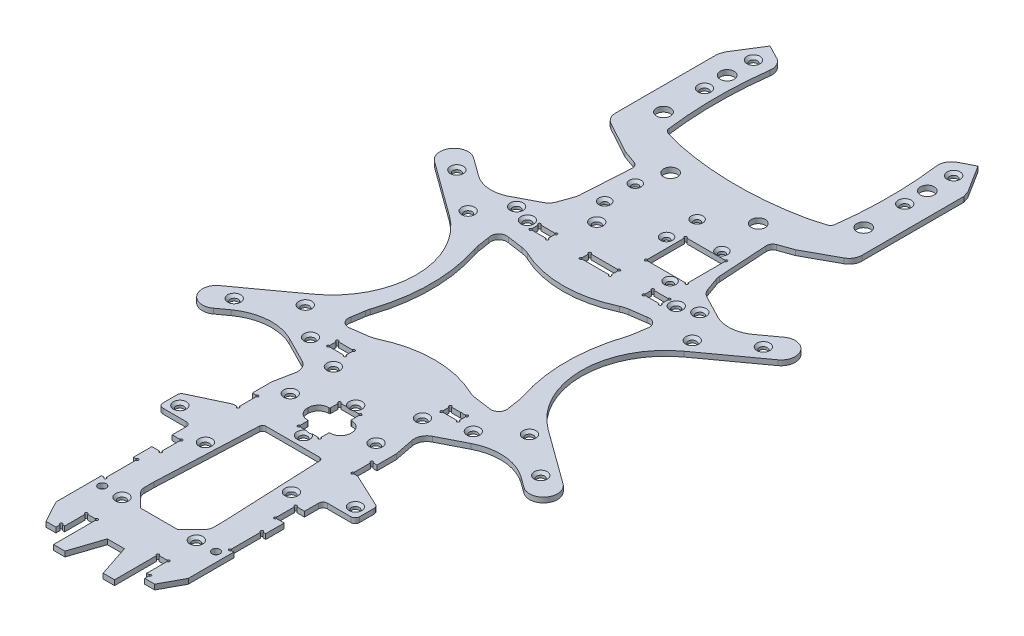
SolidWorks part; units mm, degrees
other "细节项目1"
other "细节项目5"
material "Thornel VCB-20 碳布"
ref_plane "前视基准面" through (0, 0, 0) normal (0, 0, 1) x (1, 0, 0)
ref_plane "上视基准面" through (0, 0, 0) normal (0, 1, 0) x (1, 0, 0)
ref_plane "右视基准面" through (0, 0, 0) normal (1, 0, 0) x (0, 0, -1)
sketch "草图1" plane through (0, 0, 0) normal (0, 1, 0) x (1, 0, 0)
  line L0 (-126.4995, 0) -> (116.8967, 0) construction
  line L1 (121.619, 121.619) -> (-121.619, -121.619) construction
  line L2 (0, 104.5414) -> (0, -99.6328) construction
  line L3 (-108.3893, 108.3893) -> (124.9236, -124.9236) construction
  line L4 (0, 0) -> (86.3378, -62.728) construction
  line L5 (15.4, 65.75) -> (23.6, 65.75)
  line L6 (15.4, 50.25) -> (15.4, 65.75)
  line L19 (15.4, 50.25) -> (23.6, 50.25)
  line L20 (30.4719, 81.4909) -> (48.4165, 91.3178)
  line L21 (0, 82.79) -> (0, 88.225) construction
  line L23 (-25.278, 96.1016) -> (-31.2014, 97.7723)
  line L25 (24.5, -95.1) -> (26.0011, -95.1) construction
  line L35 (67.5025, -42.245) -> (46.103, -26.6974)
  line L38 (-16.7464, -105.1066) -> (-17.9066, -103.9464) construction
  line L39 (-48.4165, 91.3178) -> (-48.4165, 134.3222)
  line L40 (-30.4719, 81.4909) -> (-48.4165, 91.3178)
  line L42 (26.0011, -95.1) -> (26.0011, -102.35)
  line L59 (-47.6512, 136.6895) -> (-40.8695, 147.4648)
  line L64 (15.4, 58) -> (27.0301, 58) construction
  line L65 (19.5, 65.75) -> (19.5, 50.25) construction
  line L66 (23.6, 65.75) -> (23.6, 50.25)
  line L69 (-39.335, 68.135) -> (3.7462, 68.135) construction
  line L72 (26.0011, -102.35) -> (22.5, -102.35)
  line L80 (-18.6137, -103.9464) -> (-19.7036, -105.0363) construction
  line L82 (4.1009, -74) -> (4.1009, -71.0475)
  line L83 (-3.6009, -74.5) -> (3.6009, -74.5)
  line L84 (3.6009, -58.5) -> (-3.5991, -58.5)
  line L85 (4.1009, -59) -> (4.1009, -61.9525)
  line L86 (-4.1009, -74) -> (-4.1009, -71.0461)
  line L87 (-4.1009, -61.9511) -> (-4.1009, -58.9981)
  line L88 (-4.5484, -70.6961) -> (-4.4509, -70.6961)
  line L89 (-8.5484, -66.6961) -> (-8.5484, -66.3011)
  line L90 (8.5484, -66.6975) -> (8.5484, -66.3025)
  line L91 (4.4509, -70.6975) -> (4.5484, -70.6975)
  line L92 (4.5484, -62.3025) -> (4.4509, -62.3025)
  line L93 (-4.5484, -62.3011) -> (-4.4509, -62.3011)
  line L97 (19, -62.5) -> (19, -100.5) construction
  line L98 (19, -100.5) -> (-19, -100.5) construction
  line L99 (-19, -62.5) -> (-19, -100.5) construction
  line L100 (22.5, -102.35) -> (22.5, -110.35)
  line L101 (16.1, -146) -> (16.1, -154.5)
  line L102 (16.1, -146) -> (12, -146)
  line L103 (12, -146) -> (12, -163)
  line L104 (17.45, -154.5) -> (16.1, -154.5)
  line L105 (17.45, -156.6) -> (17.45, -154.5)
  line L106 (-3.3584, -150.5) -> (-7.5, -163)
  line L107 (-7.5, -163) -> (-12, -163)
  line L108 (21.3534, -156.6) -> (17.45, -156.6)
  line L109 (-17.45, -156.6) -> (-17.45, -154.5)
  line L110 (-17.45, -154.5) -> (-16.1, -154.5)
  line L111 (-12, -146) -> (-12, -163)
  line L112 (-16.1, -146) -> (-12, -146)
  line L113 (-16.1, -146) -> (-16.1, -154.5)
  line L114 (7.5, -163) -> (12, -163)
  line L115 (-3.3584, -150.5) -> (3.3584, -150.5)
  line L116 (3.3584, -150.5) -> (7.5, -163)
  line L117 (-21.3534, -156.6) -> (-17.45, -156.6)
  line L118 (-13.5761, -121.8546) -> (-11.8487, -82.2911)
  line L119 (-12.5918, -128.1539) -> (-7.25, -133.5)
  line L120 (-7.25, -133.5) -> (7.25, -133.5)
  line L121 (-13.5793, -125.7684) -> (-13.5793, -122.0018)
  line L122 (22.5, -110.35) -> (26.0011, -110.35)
  line L123 (26.0011, -130.1) -> (26.0011, -148.0463)
  line L124 (26.0011, -148.0463) -> (21.3534, -156.6)
  line L125 (-26.0011, -148.0463) -> (-21.3534, -156.6)
  line L126 (-26.0011, -130.1) -> (-26.0011, -148.0463)
  line L127 (26.0011, -110.35) -> (26.0011, -117.6)
  line L128 (26.0011, -117.6) -> (24.5011, -117.6)
  line L129 (24.5011, -117.6) -> (24.5011, -130.1)
  line L130 (24.5011, -130.1) -> (26.0011, -130.1)
  line L132 (-24.5011, -130.1) -> (-26.0011, -130.1)
  line L133 (-24.5011, -117.6) -> (-24.5011, -130.1)
  line L134 (-26.0011, -117.6) -> (-24.5011, -117.6)
  line L135 (-26.0011, -110.35) -> (-26.0011, -117.6)
  line L136 (-22.5, -110.35) -> (-26.0011, -110.35)
  line L137 (-22.5, -102.35) -> (-22.5, -110.35)
  line L138 (-26.0011, -102.35) -> (-22.5, -102.35)
  line L139 (-26.0011, -95.1) -> (-26.0011, -102.35)
  line L140 (-24.5, -95.1) -> (-26.0011, -95.1) construction
  line L142 (-67.5025, 42.245) -> (-46.103, 26.6974)
  line L143 (-67.5025, -42.245) -> (-46.103, -26.6974)
  line L149 (48.4165, 91.3178) -> (48.4165, 134.3222)
  line L150 (0, -114.8485) -> (0, -146.3095) construction
  line L151 (-10.5, -81) -> (10.5, -81)
  line L152 (12.5918, -128.1539) -> (7.25, -133.5)
  line L153 (13.5793, -125.7684) -> (13.5793, -122.0018)
  line L154 (13.5761, -121.8546) -> (11.8487, -82.2911)
  line L155 (-19, -62.5) -> (19, -62.5) construction
  line L180 (67.5025, 42.245) -> (46.103, 26.6974)
  line L181 (44.0442, 32) -> (60.2246, 43.7557) construction
  line L183 (25.278, 96.1016) -> (31.2014, 97.7723)
  line L195 (61.0368, 51.1442) -> (53.9618, 46.0039)
  line L196 (30.4719, 81.4909) -> (34.3794, 54.2815)
  line L197 (-30.4719, 81.4909) -> (-34.3794, 54.2815)
  line L198 (-61.0368, 51.1442) -> (-53.9618, 46.0039)
  line L199 (57.02, -48.2258) -> (61.0368, -51.1442)
  line L200 (24.5, -64.7956) -> (24.5, -95.1) construction
  line L201 (-24.5, -64.7956) -> (-24.5, -95.1) construction
  line L202 (-57.02, -48.2258) -> (-61.0368, -51.1442)
  line L203 (26.0011, -95.1) -> (38.6804, -95.1)
  line L204 (38.6804, -95.1) -> (38.6804, -86.6)
  line L205 (38.6804, -86.6) -> (24.5, -79.9478)
  line L207 (-38.6804, -86.6) -> (-24.5, -79.9478)
  line L208 (-38.6804, -95.1) -> (-38.6804, -86.6)
  line L209 (-26.0011, -95.1) -> (-38.6804, -95.1)
  line L210 (-24.5, -64.7956) -> (-24.5, -79.9478) construction
  line L211 (-19.7036, -114.2434) -> (-18.5434, -115.4036) construction
  line L212 (-17.8363, -115.4036) -> (-16.7464, -114.3137) construction
  line L213 (-19.85, -105.3898) -> (-19.85, -113.8898) construction
  line L214 (-16.6, -105.4602) -> (-16.6, -113.9602) construction
  line L221 (-16.6, -105.4602) -> (-16.6, -108.5148) construction
  line L222 (-16.6, -108.5148) -> (-17.1, -109.0148) construction
  line L223 (-17.1, -109.0148) -> (-17.1, -110.2648) construction
  line L224 (-17.1, -110.2648) -> (-16.6, -110.7648) construction
  line L225 (-16.6, -110.7648) -> (-16.6, -113.9602) construction
  line L226 (-19.85, -109.6398) -> (-13.2317, -109.6398) construction
  line L227 (17.1, -110.2648) -> (16.6, -110.7648) construction
  line L228 (17.1, -109.0148) -> (17.1, -110.2648) construction
  line L229 (16.6, -108.5148) -> (17.1, -109.0148) construction
  line L230 (16.6, -105.4602) -> (16.6, -108.5148) construction
  line L231 (16.7464, -105.1066) -> (17.9066, -103.9464) construction
  line L232 (18.6137, -103.9464) -> (19.7036, -105.0363) construction
  line L233 (19.85, -105.3898) -> (19.85, -113.8898) construction
  line L234 (19.7036, -114.2434) -> (18.5434, -115.4036) construction
  line L235 (17.8363, -115.4036) -> (16.7464, -114.3137) construction
  line L236 (16.6, -110.7648) -> (16.6, -113.9602) construction
  line L237 (-24.5, -72.3717) -> (-22.5, -72.3717)
  line L238 (-22.5, -72.3717) -> (-22.5, -79.9478)
  line L239 (-22.5, -79.9478) -> (-24.5, -79.9478)
  line L240 (-24.5, -64.7956) -> (-24.5, -72.3717)
  line L241 (22.5, -79.9478) -> (24.5, -79.9478)
  line L242 (24.5, -64.7956) -> (24.5, -72.3717)
  line L243 (24.5, -72.3717) -> (22.5, -72.3717)
  line L244 (22.5, -72.3717) -> (22.5, -79.9478)
  line L245 (-40.8695, 147.4648) -> (-35.5107, 144.7028)
  line L246 (-47.6512, 136.6895) -> (-48.4165, 134.3222)
  line L247 (40.8695, 147.4648) -> (35.5107, 144.7028)
  line L248 (47.6512, 136.6895) -> (40.8695, 147.4648)
  line L249 (47.6512, 136.6895) -> (48.4165, 134.3222)
  circle A0 centre (10, 10) radius 1.075
  circle A1 centre (12.75, 12.75) radius 1.075
  circle A2 centre (15.25, 15.25) radius 1.55
  circle A3 centre (-15.25, 15.25) radius 1.55
  circle A4 centre (-12.75, 12.75) radius 1.075
  circle A5 centre (-10, 10) radius 1.075
  circle A6 centre (-10, -10) radius 1.075
  circle A7 centre (-12.75, -12.75) radius 1.075
  circle A8 centre (-15.25, -15.25) radius 1.55
  circle A9 centre (15.25, -15.25) radius 1.55
  circle A10 centre (12.75, -12.75) radius 1.075
  circle A11 centre (10, -10) radius 1.075
  circle A14 centre (28, -28) radius 3.15
  circle A15 centre (-28, -28) radius 3.15
  circle A16 centre (19.5, 68.2) radius 1.3
  circle A31 centre (19.5, 47.8) radius 1.3
  circle A34 centre (17.238, 84.7633) radius 2.75
  circle A35 centre (-17.238, 84.7633) radius 2.75
  circle A36 centre (-39.335, 104.0823) radius 2.75
  circle A37 centre (-39.335, 129.0823) radius 2.75
  circle A38 centre (-28, 28) radius 3.15
  circle A39 centre (28, 28) radius 3.15
  circle A43 centre (44.0442, -32) radius 1.55
  circle A44 centre (60.2246, -43.7557) radius 1.55
  circle A47 centre (-60.2246, -43.7557) radius 1.55
  circle A65 centre (-20.5, 74.15) radius 1.3
  circle A68 centre (-20.5, 62.12) radius 1.3
  circle A71 centre (-44.0442, -32) radius 1.55
  circle A72 centre (60.2246, 43.7557) radius 1.55
  circle A73 centre (44.0442, 32) radius 1.55
  circle A74 centre (-44.0442, 32) radius 1.55
  circle A75 centre (-60.2246, 43.7557) radius 1.55
  arc A77 (61.0368, -51.1442) -> (67.5025, -42.245) centre (64.2696, -46.6946) ccw
  arc A82 (-16.6, -105.4602) -> (-16.7464, -105.1066) centre (-17.1, -105.4602) ccw construction
  arc A83 (-17.9066, -103.9464) -> (-18.6137, -103.9464) centre (-18.2602, -104.3) ccw construction
  arc A84 (-19.85, -105.3898) -> (-19.7036, -105.0363) centre (-19.35, -105.3898) cw construction
  arc A85 (-4.1009, -74) -> (-3.6009, -74.5) centre (-4.1009, -74.5) ccw
  arc A86 (4.1009, -74) -> (3.6009, -74.5) centre (4.1009, -74.5) cw
  arc A87 (4.1009, -59) -> (3.6009, -58.5) centre (4.1009, -58.5) ccw
  arc A88 (-4.1009, -58.9981) -> (-3.5991, -58.5) centre (-4.0991, -58.4981) cw
  arc A89 (8.5484, -66.3025) -> (4.5484, -62.3025) centre (4.5484, -66.3025) ccw
  arc A90 (-4.5484, -62.3011) -> (-8.5484, -66.3011) centre (-4.5484, -66.3011) ccw
  arc A91 (-4.5484, -70.6961) -> (-8.5484, -66.6961) centre (-4.5484, -66.6961) cw
  arc A92 (8.5484, -66.6975) -> (4.5484, -70.6975) centre (4.5484, -66.6975) cw
  arc A93 (4.1009, -61.9525) -> (4.4509, -62.3025) centre (4.4509, -61.9525) ccw
  arc A94 (4.1009, -71.0475) -> (4.4509, -70.6975) centre (4.4509, -71.0475) cw
  arc A95 (-4.1009, -61.9511) -> (-4.4509, -62.3011) centre (-4.4509, -61.9511) cw
  arc A96 (-4.1009, -71.0461) -> (-4.4509, -70.6961) centre (-4.4509, -71.0461) ccw
  circle A103 centre (-22.35, -133.5) radius 1.55
  circle A104 centre (22.35, -133.5) radius 1.55
  circle A105 centre (-16.9, -98.4) radius 1.55
  circle A106 centre (16.9, -98.4) radius 1.55
  arc A107 (-10.5, -81) -> (-11.8487, -82.2911) centre (-10.5, -82.35) ccw
  arc A108 (-13.5793, -122.0018) -> (-13.5761, -121.8546) centre (-10.2043, -122.0018) cw
  arc A109 (-12.5918, -128.1539) -> (-13.5793, -125.7684) centre (-10.2043, -125.7684) cw
  circle A110 centre (-14.6, -133.5) radius 1.55
  circle A111 centre (14.6, -133.5) radius 1.55
  arc A112 (12.5918, -128.1539) -> (13.5793, -125.7684) centre (10.2043, -125.7684) ccw
  arc A113 (13.5793, -122.0018) -> (13.5761, -121.8546) centre (10.2043, -122.0018) ccw
  arc A114 (10.5, -81) -> (11.8487, -82.2911) centre (10.5, -82.35) cw
  circle A143 centre (-16.866, -65.108) radius 1.55
  circle A144 centre (16.866, -65.108) radius 1.55
  circle A145 centre (0, -56.25) radius 1.55
  circle A146 centre (0, -76.75) radius 1.55
  arc A147 (61.0368, 51.1442) -> (67.5025, 42.245) centre (64.2696, 46.6946) cw
  arc A148 (46.103, 26.6974) -> (46.103, -26.6974) centre (65.4998, 0) ccw
  circle A149 centre (44.0442, -32) radius 6 construction
  arc A151 (-61.0368, 51.1442) -> (-67.5025, 42.245) centre (-64.2696, 46.6946) ccw
  arc A153 (-46.103, 26.6974) -> (-46.103, -26.6974) centre (-65.4998, 0) cw
  arc A154 (-61.0368, -51.1442) -> (-67.5025, -42.245) centre (-64.2696, -46.6946) cw
  circle A158 centre (39.335, 129.0823) radius 2.75
  circle A159 centre (39.335, 104.0823) radius 2.75
  arc A160 (-25.278, 96.1016) -> (25.278, 96.1016) centre (0, 215.2587) ccw
  circle A161 centre (-36, 43) radius 1.55
  circle A164 centre (36, 43) radius 1.55
  circle A165 centre (-32, -42) radius 1.55
  circle A166 centre (32, -42) radius 1.55
  circle A171 centre (-39.335, 139.4323) radius 1.55
  arc A178 (32.6754, 139.3072) -> (32.6419, 99.4401) centre (-122.1129, 119.5036) cw
  arc A180 (-32.6754, 139.3072) -> (-32.6419, 99.4401) centre (122.1129, 119.5036) ccw
  arc A182 (53.9618, 46.0039) -> (34.3794, 54.2815) centre (46.6659, 56.0459) cw
  arc A183 (-53.9618, 46.0039) -> (-34.3794, 54.2815) centre (-46.6659, 56.0459) ccw
  circle A185 centre (39.335, 139.4323) radius 1.55
  arc A186 (57.02, -48.2258) -> (24.5, -64.7956) centre (44.9813, -64.7956) ccw
  arc A187 (-57.02, -48.2258) -> (-24.5, -64.7956) centre (-44.9813, -64.7956) cw
  circle A188 centre (34.5, -90.85) radius 1.55
  circle A189 centre (-34.5, -90.85) radius 1.55
  circle A190 centre (39.335, 120.1823) radius 1.55
  circle A191 centre (-39.335, 120.1823) radius 1.55
  arc A192 (-19.85, -113.8898) -> (-19.7036, -114.2434) centre (-19.35, -113.8898) ccw construction
  arc A193 (-18.5434, -115.4036) -> (-17.8363, -115.4036) centre (-18.1898, -115.05) ccw construction
  arc A194 (-16.6, -113.9602) -> (-16.7464, -114.3137) centre (-17.1, -113.9602) cw construction
  arc A195 (16.6, -105.4602) -> (16.7464, -105.1066) centre (17.1, -105.4602) cw construction
  arc A196 (17.9066, -103.9464) -> (18.6137, -103.9464) centre (18.2602, -104.3) cw construction
  arc A197 (19.85, -105.3898) -> (19.7036, -105.0363) centre (19.35, -105.3898) ccw construction
  arc A198 (19.85, -113.8898) -> (19.7036, -114.2434) centre (19.35, -113.8898) cw construction
  arc A199 (18.5434, -115.4036) -> (17.8363, -115.4036) centre (18.1898, -115.05) cw construction
  arc A200 (16.6, -113.9602) -> (16.7464, -114.3137) centre (17.1, -113.9602) ccw construction
  circle A201 centre (3.8, 62.12) radius 1.3
  circle A202 centre (3.8, 74.15) radius 1.3
  arc A203 (-35.5107, 144.7028) -> (-32.6754, 139.3072) centre (-37.9442, 139.9813) cw
  arc A204 (35.5107, 144.7028) -> (32.6754, 139.3072) centre (37.9442, 139.9813) ccw
  arc A205 (32.6419, 99.4401) -> (31.2014, 97.7723) centre (30.6585, 99.6972) cw
  arc A206 (-31.2014, 97.7723) -> (-32.6419, 99.4401) centre (-30.6585, 99.6972) cw
  point P55 (32.4663, 98.1291)
  point P77 (-32.4663, 98.1291)
  point P104 (-32.5, 0)
  point P105 (32.5, 0)
  point P214 (38.6804, -90.85)
  point P354 (0, -133.5)
  point P361 (7.3036, -118.1341)
  point P364 (0, -81)
  dimension "D2" = 2.15
  dimension "D5" = 3.1
  dimension "D7" = 3.1
  dimension "D8" = 36
  dimension "D10" = 39.335
  dimension "D11" = 3.1
  dimension "D20" = 2.6
  dimension "D22" = 3.1
  dimension "D32" = 7.25
  dimension "D12" = 24.3
  dimension "D15" = 3.25
  dimension "D13" = 19.85
  dimension "D9" = 3.1
  dimension "D25" = 5.5
  dimension "D26" = 5
  dimension "D31" = 12
  dimension "D41" = 96.833
  dimension "D49" = 32
  dimension "D54" = 35.35
  dimension "D59" = 8.5
  dimension "D61" = 6.3
  dimension "D70" = 2.6
  dimension "D69" = 156.05
  dimension "D71" = 2
  dimension "D84" = 24.735
  dimension "D3" = 10
  dimension "D4" = 2.75
  dimension "D6" = 2.5
  dimension "D14" = 58
  dimension "D16" = 2.608
  dimension "D17" = 15.5
  dimension "D18" = 2.45
  dimension "D19" = 8.2
  dimension "D21" = 12.03
  dimension "D23" = 2.25
  dimension "D24" = 2.25
  dimension "D27" = 20
  dimension "D28" = 25
  dimension "D29" = 19.5
  dimension "D30" = 32
  dimension "D33" = 1.5
  dimension "D34" = 2.1
  dimension "D35" = 8.5
  dimension "D36" = 4.5
  dimension "D37" = 4
  dimension "D38" = 4.1
  dimension "D39" = 8
  dimension "D40" = 65
  dimension "D42" = 10.5
  dimension "D43" = 43
  dimension "D44" = 52.5
  dimension "D45" = 58.5
  dimension "D46" = 7.2
  dimension "D47" = 16
  dimension "D48" = 62.5
  dimension "D50" = 38
  dimension "D51" = 139.4323
  dimension "D52" = 36
  dimension "D53" = 42
  dimension "D55" = 90.85
  dimension "D56" = 5.5
  dimension "D57" = 38
  dimension "D58" = 34.5
  dimension "D60" = 56
  dimension "D62" = 7.25
  dimension "D63" = 19.25
  dimension "D64" = 8.5
  dimension "D65" = 1.25
  dimension "D66" = 0.5
  dimension "D67" = 2
  dimension "D68" = 20.5
  dimension "D72" = 29.2
  dimension "D73" = 7.75
  dimension "D74" = 1.35
  dimension "D75" = 24
  dimension "D76" = 6.4
  dimension "D77" = 12.5
  dimension "D78" = 6.5
  dimension "D79" = 92.5
  dimension "D80" = 12.5
  dimension "D81" = 133.5
  dimension "D82" = 4.5
  dimension "D83" = 272.9323
extrude "凸台-拉伸1" add sketch "草图1" along normal blind 2
sketch "草图6" plane through (0, 2, 0) normal (0, 1, 0) x (1, 0, 0)
  line L40 (-58.8867, 0) -> (57.6096, 0) construction
  line L41 (0, 29.8455) -> (0, -115.5328) construction
  line L42 (22.5859, -13.8118) -> (4.3699, 0)
  line L43 (22.5859, 13.8118) -> (4.3699, 0)
  line L44 (-22.5859, 13.8118) -> (-4.3699, 0)
  line L45 (-22.5859, -13.8118) -> (-4.3699, 0)
  line L46 (-11.5388, -19.5881) -> (0, -4.3699)
  line L47 (11.5388, -19.5881) -> (0, -4.3699)
  line L48 (11.5388, 19.5881) -> (0, 4.3699)
  line L49 (-11.5388, 19.5881) -> (0, 4.3699)
  line L50 (0, 0) -> (43.5528, -43.5528) construction
  arc A48 (22.5859, 13.8118) -> (28.8648, 17.1963) centre (41.8919, -14.4887) cw
  arc A49 (28.8648, 17.1963) -> (28.8648, -17.1963) centre (91.8849, 0) ccw
  arc A50 (22.5859, -13.8118) -> (28.8648, -17.1963) centre (41.8919, 14.4887) ccw
  arc A51 (13.7761, -22.9243) -> (-13.7761, -22.9243) centre (0, -91.9966) ccw
  arc A52 (-22.5859, -13.8118) -> (-28.8648, -17.1963) centre (-41.8919, 14.4887) cw
  arc A53 (-28.8648, 17.1963) -> (-28.8648, -17.1963) centre (-91.8849, 0) cw
  arc A54 (-22.5859, 13.8118) -> (-28.8648, 17.1963) centre (-41.8919, -14.4887) ccw
  arc A55 (11.5388, -19.5881) -> (13.7761, -22.9243) centre (-16.057, -40.512) cw
  arc A56 (-11.5388, -19.5881) -> (-13.7761, -22.9243) centre (16.057, -40.512) ccw
  arc A57 (-11.5388, 19.5881) -> (-13.7761, 22.9243) centre (16.057, 40.512) cw
  arc A58 (13.7761, 22.9243) -> (-13.7761, 22.9243) centre (0, 91.9966) cw
  arc A59 (11.5388, 19.5881) -> (13.7761, 22.9243) centre (-16.057, 40.512) ccw
  point P79 (0, 0)
extrude "减重" cut sketch "草图6" against normal up to next
sketch "减重-2-草图" plane through (0, 0, 0) normal (0, 1, 0) x (1, 0, 0)
  line L0 (-20.9845, 30.1828) -> (-28, 31.15)
  line L1 (-31.15, 28) -> (-30.2498, 22.1218)
  line L2 (0, 0) -> (-85.1983, 0) construction
  line L3 (0, 0) -> (0, 222.2014) construction
  line L4 (31.15, 28) -> (30.2498, 22.1218)
  line L5 (20.9845, 30.1828) -> (28, 31.15)
  line L6 (20.9845, -30.1828) -> (28, -31.15)
  line L7 (31.15, -28) -> (30.2498, -22.1218)
  line L8 (-31.15, -28) -> (-30.2498, -22.1218)
  line L9 (-20.9845, -30.1828) -> (-28, -31.15)
  circle A0 centre (-28, 28) radius 3.15 construction
  arc A1 (-31.15, 28) -> (-28, 31.15) centre (-28, 28) cw
  arc A2 (31.15, 28) -> (28, 31.15) centre (28, 28) ccw
  arc A3 (31.15, -28) -> (28, -31.15) centre (28, -28) cw
  arc A4 (-31.15, -28) -> (-28, -31.15) centre (-28, -28) ccw
  arc A5 (-29.86, 20.4977) -> (-29.86, -20.4977) centre (-91.8849, 0) cw
  arc A6 (-18.059, -29.3089) -> (18.059, -29.3089) centre (0, -67.3193) cw
  arc A7 (29.86, -20.4977) -> (29.86, 20.4977) centre (91.8849, 0) cw
  arc A8 (-18.059, 29.3089) -> (18.059, 29.3089) centre (0, 67.3193) ccw
  arc A9 (-28.8648, -17.1963) -> (-28.8648, 17.1963) centre (-91.8849, 0) ccw construction
  arc A10 (28.8648, 17.1963) -> (28.8648, -17.1963) centre (91.8849, 0) ccw construction
  arc A13 (30.2498, -22.1218) -> (29.86, -20.4977) centre (20.3651, -23.6355) ccw
  arc A14 (20.9845, -30.1828) -> (18.059, -29.3089) centre (22.3504, -20.2765) cw
  arc A15 (-20.9845, -30.1828) -> (-18.059, -29.3089) centre (-22.3504, -20.2765) ccw
  arc A16 (-30.2498, -22.1218) -> (-29.86, -20.4977) centre (-20.3651, -23.6355) cw
  arc A17 (30.2498, 22.1218) -> (29.86, 20.4977) centre (20.3651, 23.6355) cw
  arc A18 (-30.2498, 22.1218) -> (-29.86, 20.4977) centre (-20.3651, 23.6355) ccw
  arc A19 (20.9845, 30.1828) -> (18.059, 29.3089) centre (22.3504, 20.2765) ccw
  arc A20 (-20.9845, 30.1828) -> (-18.059, 29.3089) centre (-22.3504, 20.2765) cw
  point P39 (30.1184, -21.2637)
  point P42 (19.3706, -29.9602)
  point P45 (-19.3706, -29.9602)
  point P48 (-30.1184, -21.2637)
  point P51 (30.1184, 21.2637)
  point P54 (-30.1184, 21.2637)
  point P57 (19.3706, 29.9602)
  point P60 (-19.3706, 29.9602)
  dimension "D1" = 10
extrude "切除-拉伸2" cut sketch "减重-2-草图" along normal through all both and the other way through all
fillet "圆角1" radius 5 6 edges at (-25.278, 1, -96.1016) (25.278, 1, -96.1016) (48.4165, 1, -91.3178) (-48.4165, 1, -91.3178) (-30.4719, 1, -81.4909) (30.4719, 1, -81.4909)
sketch "草图7" plane through (0, 2, 0) normal (0, 1, 0) x (1, 0, 0)
  line L0 (-81.2345, 0) -> (102.1666, 0) construction
  line L1 (0, 63.5408) -> (0, -83.9036) construction
  line L2 (34, -3.25) -> (30.5, -3.25) construction
  line L3 (-34, 3.25) -> (-30.5, 3.25) construction
  line L4 (-34, 3.25) -> (-34, -3.25) construction
  line L5 (-34, -3.25) -> (-30.5, -3.25) construction
  line L6 (-30.5, 3.25) -> (-30.5, -3.25) construction
  line L7 (30.5, 3.25) -> (30.5, -3.25) construction
  line L8 (34, 3.25) -> (30.5, 3.25) construction
  line L9 (34, 3.25) -> (34, -3.25) construction
  line L10 (19, -38) -> (25.5, -38)
  line L11 (-25.5, 41.5) -> (-19, 41.5)
  line L12 (-25.5, 41.5) -> (-25.5, 38)
  line L13 (-25.5, 38) -> (-19, 38)
  line L14 (-19, 41.5) -> (-19, 38)
  line L15 (19, -38) -> (19, -41.5)
  line L16 (19, -41.5) -> (25.5, -41.5)
  line L17 (25.5, -38) -> (25.5, -41.5)
  line L18 (-19, -38) -> (-19, -41.5)
  line L19 (-19, -41.5) -> (-25.5, -41.5)
  line L20 (-25.5, -38) -> (-25.5, -41.5)
  line L21 (-19, -38) -> (-25.5, -38)
  line L22 (25.5, 38) -> (19, 38)
  line L23 (19, 41.5) -> (19, 38)
  line L24 (25.5, 41.5) -> (19, 41.5)
  line L25 (25.5, 41.5) -> (25.5, 38)
  line L26 (-5.75, -38) -> (5.75, -38) construction
  line L27 (5.75, -38) -> (5.75, -41.5) construction
  line L28 (5.75, -41.5) -> (-5.75, -41.5) construction
  line L29 (-5.75, -41.5) -> (-5.75, -38) construction
  line L30 (5.75, 41.5) -> (-5.75, 41.5)
  line L31 (5.75, 38) -> (5.75, 41.5)
  line L32 (-5.75, 38) -> (5.75, 38)
  line L33 (-5.75, 41.5) -> (-5.75, 38)
  point P26 (19, -39.75)
  dimension "D1" = 3.5
  dimension "D2" = 6.5
  dimension "D3" = 30.5
  dimension "D4" = 38
  dimension "D5" = 19
  dimension "D6" = 38
  dimension "D7" = 5.75
extrude "保护壳固定点" cut sketch "草图7" against normal up to next
sketch "草图8" plane through (0, 0, 0) normal (0, 1, 0) x (1, 0, 0)
  line L1 (15.4, 50.25) -> (23.6, 50.25) construction
  line L5 (0, 0) -> (0, 133.3353) construction
  line L6 (0, 0) -> (133.1914, 0) construction
  line L7 (7.65, 65.75) -> (15.4, 65.75)
  line L8 (15.4, 65.75) -> (15.4, 50.25) construction
  line L9 (15.4, 65.75) -> (15.4, 50.25)
  line L10 (15.4, 50.25) -> (7.65, 50.25)
  line L11 (7.65, 50.25) -> (7.65, 65.75)
  line L12 (14.15, 65.75) -> (14.15, 50.25) construction
  circle A0 centre (23.5, -39.4628) radius 1.55
  circle A1 centre (0, -56.25) radius 1.55 construction
  circle A2 centre (-29.25, 40.5) radius 1.55
  circle A4 centre (-17.5, -47.5) radius 1.55
  circle A6 centre (29.25, 40.5) radius 1.55
  circle A7 centre (17.5, -47.5) radius 1.55
  circle A8 centre (29.25, 40.5) radius 1.55
  dimension "D3" = 3.1
  dimension "D9" = 40.5
  dimension "D12" = 3.1
  dimension "D1" = 16.7872
  dimension "D2" = 23.5
  dimension "D4" = 1.25
  dimension "D6" = 6.5
  dimension "D7" = 15.5
  dimension "D8" = 29.25
  dimension "D10" = 47.5
  dimension "D11" = 17.5
extrude "计算机板接口和分电PCB接口" cut sketch "草图8" along normal through all contours L11 L10 L9 L7 | A2 | A4 | A7 | A6 | A0 | A0 region at (11.525, 0, -58) region at (23.5, 0, 39.4628) region at (-29.25, 0, -40.5) region at (-17.5, 0, 47.5) region at (29.25, 0, -40.5) region at (17.5, 0, 47.5)
fillet "圆角2" radius 1.75 8 edges at (-26.0011, 1, 95.1) (-38.6804, 1, 95.1) (-38.6804, 1, 86.6) (38.6804, 1, 86.6) (38.6804, 1, 95.1) (26.0011, 1, 95.1) (24.5, 1, 79.9478) (-24.5, 1, 79.9478)
sketch "草图12" plane through (0, 0, 0) normal (0, 1, 0) x (1, 0, 0)
  line L0 (26.7, 40.5) -> (-26.7, 40.5) construction
  circle A10 centre (-15, 53.5) radius 1.55
  dimension "D1" = 3.1
  dimension "D2" = 53.5
  dimension "D3" = 15
extrude "计算机板安装孔-旧的太难用了" cut sketch "草图12" along normal through all
sketch "边缘二次裁切-减重-草图" plane through (0, 0, 0) normal (0, 1, 0) x (1, 0, 0)
  line L0 (-26.3649, 78.6977) -> (-27.5605, 59.15)
  line L1 (-27.8403, 57.7795) -> (-29.754, 52.4001)
  line L2 (-32.155, 49.6414) -> (-41.6968, 44.6713)
  line L3 (-28.0234, 81.2061) -> (-33.5123, 83.1559)
  line L4 (-33.5123, 83.1559) -> (-41.6968, 44.6713)
  line L5 (0, 0) -> (0, 176.889) construction
  line L6 (-26.25, 80.5762) -> (-26.25, 105.0808) construction
  line L7 (28.0234, 81.2061) -> (33.5123, 83.1559)
  line L8 (26.3649, 78.6977) -> (27.5605, 59.15)
  line L9 (27.8403, 57.7795) -> (29.754, 52.4001)
  line L10 (32.155, 49.6414) -> (41.6968, 44.6713)
  line L11 (33.5123, 83.1559) -> (41.6968, 44.6713)
  line L12 (-35.683, -46.5466) -> (-25.6169, -51.6755)
  line L13 (-22.9814, -57.0983) -> (-24.5, -64.7956)
  line L14 (-22.25, -53.391) -> (-22.25, -41.5) construction
  line L15 (-35.683, -46.5466) -> (-35.683, -64.7956)
  line L16 (-35.683, -64.7956) -> (-24.5, -64.7956)
  line L21 (-45.8181, 89.8949) -> (-33.5123, 83.1559) construction
  line L22 (35.683, -46.5466) -> (25.6169, -51.6755)
  line L23 (35.683, -46.5466) -> (35.683, -64.7956)
  line L24 (35.683, -64.7956) -> (24.5, -64.7956)
  line L25 (22.9814, -57.0983) -> (24.5, -64.7956)
  line L28 (0, 0) -> (-89.0445, 0) construction
  line L29 (-13.8246, 34.5028) -> (0, 30.5288) construction
  line L32 (-13.8246, 34.5028) -> (-11.6065, 42.2193) construction
  line L33 (-11.6065, 42.2193) -> (0, 44.9377) construction
  line L34 (13.8246, 34.5028) -> (0, 30.5288) construction
  line L35 (13.8246, 34.5028) -> (11.6065, 42.2193) construction
  line L36 (11.6065, 42.2193) -> (0, 44.9377) construction
  arc A3 (-26.3649, 78.6977) -> (-28.0234, 81.2061) centre (-28.8602, 78.8503) ccw
  arc A4 (-29.754, 52.4001) -> (-32.155, 49.6414) centre (-34.4648, 54.0759) cw
  arc A5 (-27.5605, 59.15) -> (-27.8403, 57.7795) centre (-32.5512, 59.4553) cw
  arc A6 (26.3649, 78.6977) -> (28.0234, 81.2061) centre (28.8602, 78.8503) cw
  arc A7 (27.5605, 59.15) -> (27.8403, 57.7795) centre (32.5512, 59.4553) ccw
  arc A8 (29.754, 52.4001) -> (32.155, 49.6414) centre (34.4648, 54.0759) ccw
  circle A10 centre (-17.5, -47.5) radius 1.55 construction
  arc A11 (-53.9618, 46.0039) -> (-34.3794, 54.2815) centre (-46.6659, 56.0459) ccw construction
  arc A12 (-24.5, -64.7956) -> (-57.02, -48.2258) centre (-44.9813, -64.7956) ccw construction
  arc A13 (-25.6169, -51.6755) -> (-22.9814, -57.0983) centre (-27.8869, -56.1305) cw
  arc A14 (25.6169, -51.6755) -> (22.9814, -57.0983) centre (27.8869, -56.1305) ccw
  circle A15 centre (-20.5, 74.15) radius 1.3 construction
  arc A16 (33.5123, 83.1559) -> (30.9647, 78.0597) centre (35.9139, 78.7704) ccw construction
  point P24 (-27.6036, 58.445)
  point P39 (0, 0)
  point P56 (-35.683, -46.5466)
  dimension "D4" = 2.5
  dimension "D5" = 5
  dimension "D1" = 5
  dimension "D7" = 15
  dimension "D2" = 3.5
  dimension "D3" = 5.75
  dimension "D6" = 4.75
chamfer "沉头螺丝位" distance 1 angle 45 37 edges at (14.6, 2, 135.05) (-14.6, 2, 131.95) (0, 2, 57.8) (0, 2, 78.3) (19.5, 2, -49.1) (19.5, 2, -69.5) (-20.5, 2, -63.42) (-20.5, 2, -72.85) (60.2246, 2, -45.3057) (44.0442, 2, -33.55) (36, 2, -44.55) (-60.2246, 2, -42.2057) (-36, 2, -41.45) (-44.0442, 2, -30.45) (-32, 2, 43.55) (-44.0442, 2, 30.45) (-60.2246, 2, 42.2057) (60.2246, 2, 45.3057) (44.0442, 2, 33.55) (32, 2, 40.45) (16.866, 2, 63.558) (-16.866, 2, 66.658) (-16.9, 2, 99.95) (16.9, 2, 96.85) (34.5, 2, 92.4) (-34.5, 2, 89.3) (39.335, 2, -137.8823) (-39.335, 2, -137.8823) (29.25, 2, -38.95) (-29.25, 2, -38.95) (-17.5, 2, 49.05) (17.5, 2, 49.05) (39.335, 2, -118.6323) (-39.335, 2, -121.7323) (3.8, 2, -75.45) (3.8, 2, -60.82) (-15, 2, -51.95)
extrude "边缘二次裁切-减重" cut sketch "边缘二次裁切-减重-草图" along normal through all
sketch "这个是因为刀切不了直角" plane through (0, 2, 0) normal (0, 1, 0) x (1, 0, 0)
  line L0 (-5.75, 41.5) -> (-5.75, 38) construction
  line L1 (-17.45, -156.6) -> (-17.45, -154.5) construction
  line L2 (0, 0) -> (0, -194.9857) construction
  circle A0 centre (7.65, 65.75) radius 0.5
  circle A1 centre (7.65, 50.25) radius 0.5
  circle A2 centre (-25.5, 41.5) radius 0.5
  circle A3 centre (-19, 41.5) radius 0.5
  circle A4 centre (-25.5, 38) radius 0.5
  circle A5 centre (-19, 38) radius 0.5
  circle A31 centre (-22.5, -72.3717) radius 0.5
  circle A33 centre (-22.5, -79.9478) radius 0.5
  circle A35 centre (-22.5, -102.35) radius 0.5
  circle A37 centre (-22.5, -110.35) radius 0.5
  circle A39 centre (-24.5011, -117.6) radius 0.5
  circle A40 centre (-16.1, -146) radius 0.5
  circle A41 centre (-24.5011, -130.1) radius 0.5
  circle A42 centre (-12, -146) radius 0.5
  circle A43 centre (-17.45, -154.5) radius 0.5
  circle A47 centre (17.45, -154.5) radius 0.5
  circle A48 centre (12, -146) radius 0.5
  circle A49 centre (24.5011, -130.1) radius 0.5
  circle A50 centre (16.1, -146) radius 0.5
  circle A51 centre (24.5011, -117.6) radius 0.5
  circle A52 centre (22.5, -110.35) radius 0.5
  circle A53 centre (22.5, -102.35) radius 0.5
  circle A54 centre (22.5, -79.9478) radius 0.5
  circle A55 centre (22.5, -72.3717) radius 0.5
  circle A62 centre (19, 38) radius 0.5
  circle A63 centre (25.5, 38) radius 0.5
  circle A64 centre (19, 41.5) radius 0.5
  circle A65 centre (25.5, 41.5) radius 0.5
  circle A72 centre (23.6, 65.75) radius 0.5
  circle A73 centre (23.6, 50.25) radius 0.5
  circle A78 centre (-25.5, -38) radius 0.5
  circle A79 centre (-25.5, -41.5) radius 0.5
  circle A80 centre (-19, -38) radius 0.5
  circle A81 centre (-19, -41.5) radius 0.5
  circle A82 centre (19, -38) radius 0.5
  circle A83 centre (19, -41.5) radius 0.5
  circle A84 centre (25.5, -38) radius 0.5
  circle A85 centre (25.5, -41.5) radius 0.5
  circle A86 centre (-5.75, 41.5) radius 0.5
  circle A87 centre (-5.75, 38) radius 0.5
  circle A88 centre (5.75, 41.5) radius 0.5
  circle A89 centre (5.75, 38) radius 0.5
  dimension "D1" = 1
extrude "直角约束" cut sketch "这个是因为刀切不了直角" against normal through all
